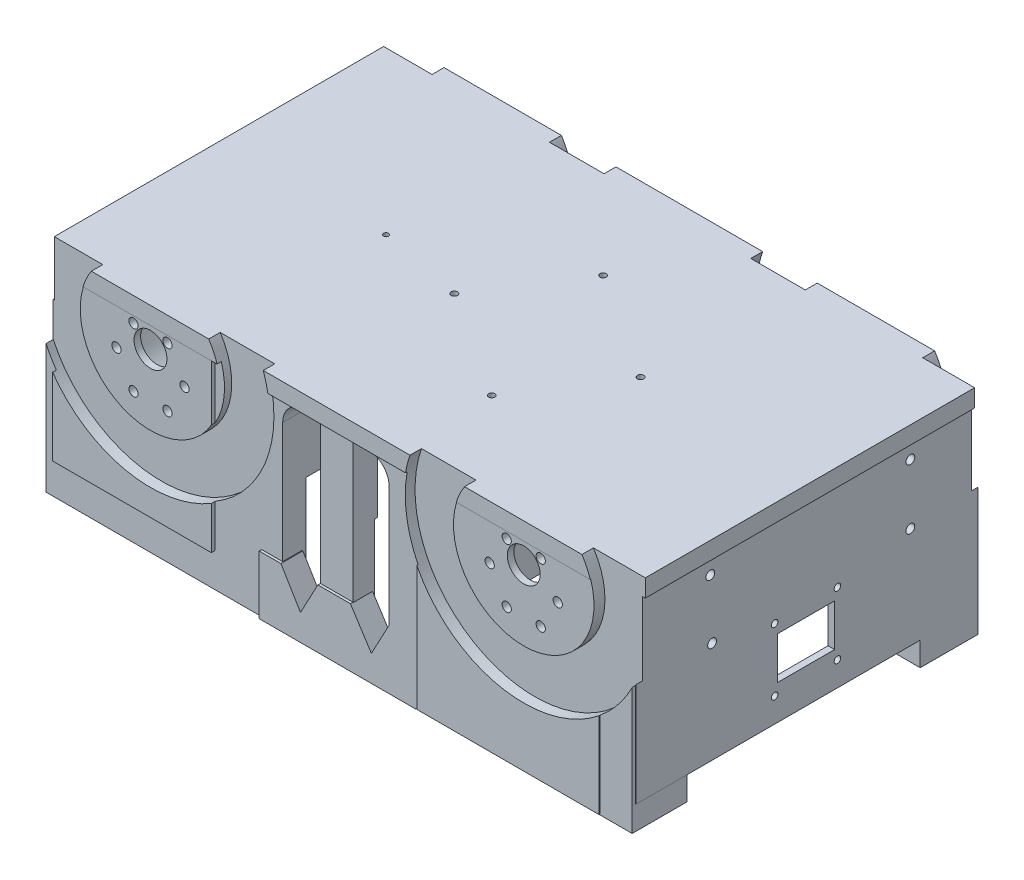
SolidWorks part; units mm, degrees
ref_plane "Front Plane" through (0, 0, 0) normal (0, 0, 1) x (1, 0, 0)
ref_plane "Top Plane" through (0, 0, 0) normal (0, 1, 0) x (1, 0, 0)
ref_plane "Right Plane" through (0, 0, 0) normal (1, 0, 0) x (0, 0, -1)
sketch "MotorHoldersSketch" plane through (0, 0, 0) normal (0, 0, 1) x (1, 0, 0)
  line L0 (0, 0) -> (170, 0) construction
  line L1 (0, 0) -> (0, 23.41) construction
  line L2 (170, 0) -> (170, 23.41) construction
  circle A0 centre (0, 0) radius 23.41
  circle A1 centre (170, 0) radius 23.41
ref_axis "MotorCenterAxis1" through (0, 0, 0) along (0, 0, 1)
ref_axis "MotorCenterAxis2" through (170, 0, 0) along (0, 0, 1)
extrude "MotorHolders" add sketch "MotorHoldersSketch" along normal blind 80 and the other way blind 80
sketch "Sketch3" plane through (0, 0, 0) normal (0, 0, 1) x (1, 0, 0)
  line L1 (1.9406, 21.133) -> (168.3435, 21.133)
  line L2 (1.9406, 21.133) -> (1.9406, 18.3155)
  line L3 (1.9406, 18.3155) -> (168.3435, 18.3155)
  line L4 (168.3435, 21.133) -> (168.3435, 18.3155)
sketch "Sketch4" plane through (0, 0, 0) normal (0, 1, 0) x (1, 0, 0)
  line L1 (221.2811, -76.3794) -> (-41.4939, -76.3794)
  line L2 (221.2811, -76.3794) -> (221.2811, 76.7331)
  line L3 (221.2811, 76.7331) -> (-41.4939, 76.7331)
  line L4 (-41.4939, -76.3794) -> (-41.4939, 76.7331)
extrude "Cut-Extrude1" cut sketch "Sketch4" against normal blind 26
ref_axis "Axis3" through (170, 0, 0) along (0, -1, 0)
sketch3d "ReferencePlanePosition"
  line L0 (170, 0, 0) -> (170, -34.8293, 0)
  line L1 (170, 0, 0) -> (170, -38.994, 0) construction
ref_plane "ReferencePlane" through (170, -34.8293, 0) normal (0, -1, 0) x (-1, 0, 0)
sketch "Sketch6" plane through (170, -34.8293, 0) normal (0, -1, 0) x (-1, 0, 0)
  line L1 (219.5858, 78.949) -> (112.1002, 78.949)
  line L2 (219.5858, 78.949) -> (219.5858, 65.5282)
  line L3 (219.5858, 65.5282) -> (112.1002, 65.5282)
  line L4 (112.1002, 78.949) -> (112.1002, 65.5282)
  line L5 (219.3147, -40.0209) -> (111.499, -40.0209)
  line L6 (219.3147, -40.0209) -> (219.3147, -78.2822)
  line L7 (219.3147, -78.2822) -> (111.499, -78.2822)
  line L8 (111.499, -40.0209) -> (111.499, -78.2822)
  line L9 (61.4891, 77.8627) -> (19.9904, 77.8627)
  line L10 (61.4891, 77.8627) -> (61.4891, 40.7512)
  line L11 (61.4891, 40.7512) -> (19.9904, 40.7512)
  line L12 (19.9904, 77.8627) -> (19.9904, 40.7512)
  line L13 (61.8484, -44.1716) -> (20.0852, -44.1716)
  line L14 (61.8484, -44.1716) -> (61.8484, -79.4437)
  line L15 (61.8484, -79.4437) -> (20.0852, -79.4437)
  line L16 (20.0852, -44.1716) -> (20.0852, -79.4437)
  line L17 (213.765, 73.0364) -> (192.9548, 73.0364)
  line L18 (213.765, 73.0364) -> (213.765, 71.0153)
  line L19 (213.765, 71.0153) -> (192.9548, 71.0153)
  line L20 (192.9548, 73.0364) -> (192.9548, 71.0153)
  line L21 (41.3552, 69.1777) -> (28.5109, 69.1777)
  line L22 (41.3552, 69.1777) -> (41.3552, 50.8413)
  line L23 (41.3552, 50.8413) -> (28.5109, 50.8413)
  line L24 (28.5109, 69.1777) -> (28.5109, 50.8413)
  line L25 (43.3068, -72.8101) -> (32.1723, -72.8101)
  line L26 (43.3068, -72.8101) -> (43.3068, -54.7747)
  line L27 (43.3068, -54.7747) -> (32.1723, -54.7747)
  line L28 (32.1723, -72.8101) -> (32.1723, -54.7747)
  line L29 (211.9411, -70.4881) -> (201.0982, -70.4881)
  line L30 (211.9411, -70.4881) -> (211.9411, -60.1404)
  line L31 (211.9411, -60.1404) -> (201.0982, -60.1404)
  line L32 (201.0982, -70.4881) -> (201.0982, -60.1404)
  line L33 (97.1795, 78.949) -> (79.4162, 78.949)
  line L34 (97.1795, 78.949) -> (97.1795, 67.7632)
  line L35 (97.1795, 67.7632) -> (79.4162, 67.7632)
  line L36 (79.4162, 78.949) -> (79.4162, 67.7632)
  line L37 (58.6711, 51.3198) -> (53.8697, 51.3198)
  line L38 (58.6711, 51.3198) -> (58.6711, 67.7632)
  line L39 (58.6711, 67.7632) -> (53.8697, 67.7632)
  line L40 (53.8697, 51.3198) -> (53.8697, 67.7632)
  line L41 (94.2281, -78.2822) -> (79.4162, -78.2822)
  line L42 (94.2281, -78.2822) -> (94.2281, -67.2515)
  line L43 (94.2281, -67.2515) -> (79.4162, -67.2515)
  line L44 (79.4162, -78.2822) -> (79.4162, -67.2515)
  line L45 (56.3648, -69.8638) -> (51.7107, -69.8638)
  line L46 (56.3648, -69.8638) -> (56.3648, -55.4273)
  line L47 (56.3648, -55.4273) -> (51.7107, -55.4273)
  line L48 (51.7107, -69.8638) -> (51.7107, -55.4273)
  line L49 (-20.7001, -79.4437) -> (-48.8506, -79.4437)
  line L50 (-20.7001, -79.4437) -> (-20.7001, -54.5097)
  line L51 (-20.7001, -54.5097) -> (-48.8506, -54.5097)
  line L52 (-48.8506, -79.4437) -> (-48.8506, -54.5097)
  line L53 (-18.3873, 77.8627) -> (-49.0581, 77.8627)
  line L54 (-18.3873, 77.8627) -> (-18.3873, 51.5325)
  line L55 (-18.3873, 51.5325) -> (-49.0581, 51.5325)
  line L56 (-49.0581, 77.8627) -> (-49.0581, 51.5325)
  line L57 (-41.8141, -72.8101) -> (-31.6362, -72.8101)
  line L58 (-41.8141, -72.8101) -> (-41.8141, -62.9794)
  line L59 (-41.8141, -62.9794) -> (-31.6362, -62.9794)
  line L60 (-31.6362, -72.8101) -> (-31.6362, -62.9794)
  line L61 (-31.6362, 69.1777) -> (-41.5347, 69.1777)
  line L62 (-31.6362, 69.1777) -> (-31.6362, 58.5421)
  line L63 (-31.6362, 58.5421) -> (-41.5347, 58.5421)
  line L64 (-41.5347, 69.1777) -> (-41.5347, 58.5421)
extrude "PowerBankHolders" add sketch "Sketch6" along normal blind 40 and the other way blind 59 separate body
sketch3d "3DSketch3"
  line L0 (170, 0, 0) -> (170, -64.5, 0) construction
ref_plane "Plane2" through (170, -64.5, 0) normal (0, -1, 0) x (-1, 0, 0)
sketch "Sketch7" plane through (170, -64.5, 0) normal (0, -1, 0) x (-1, 0, 0)
  line L1 (-9.5047, -80.801) -> (181.32, -80.801)
  line L2 (-9.5047, -80.801) -> (-9.5047, 73.8662)
  line L3 (-9.5047, 73.8662) -> (181.32, 73.8662)
  line L4 (181.32, -80.801) -> (181.32, 73.8662)
  line L5 (151.8712, -54.3972) -> (26.5361, -54.3972)
  line L6 (151.8712, -54.3972) -> (151.8712, 46.2413)
  line L7 (151.8712, 46.2413) -> (26.5361, 46.2413)
  line L8 (26.5361, -54.3972) -> (26.5361, 46.2413)
ref_point "Point1"
ref_point "Point2"
sketch3d "3DSketch11"
  line L0 (0, 0, -80) -> (170, 0, 80) construction
  point P4 (85, 0, 0)
sketch "MotorHolderExtrudeSketch" plane through (0, 0, 0) normal (0, 0, 1) x (1, 0, 0)
  circle A0 centre (170, 0) radius 20.415
  circle A1 centre (0, 0) radius 20.415
  circle A3 centre (0, 0) radius 23.41 construction
  circle A4 centre (170, 0) radius 23.41 construction
ref_point "TopOfMotors"
ref_plane "TangentToTopOfMotors" through (0, -20.415, 0) normal (0, 1, 0) x (1, 0, 0)
ref_axis "Axis4" through (85, 0, 0) along (0, -1, 0)
ref_plane "BottomOfPowerBankRegion" through (0, -20.425, 0) normal (0, 1, 0) x (1, 0, 0)
ref_point "CenterAtBottomOfPowerBank"
ref_plane "TopOfPowerBankPlane" through (0, -54.425, 0) normal (0, 1, 0) x (1, 0, 0)
sketch "Sketch13" plane through (0, -54.425, 0) normal (0, 1, 0) x (1, 0, 0)
  line L1 (-19.4498, 72.5454) -> (166.1636, 72.5454)
  line L2 (-19.4498, 72.5454) -> (-19.4498, -78.2051)
  line L3 (-19.4498, -78.2051) -> (166.1636, -78.2051)
  line L4 (166.1636, 72.5454) -> (166.1636, -78.2051)
  line L5 (19.3173, -49.583) -> (137.9607, -49.583)
  line L6 (19.3173, -49.583) -> (19.3173, -21.0549)
  line L7 (19.3173, -21.0549) -> (137.9607, -21.0549)
  line L8 (137.9607, -49.583) -> (137.9607, -21.0549)
  line L9 (19.3173, 56.6778) -> (137.9607, 56.6778)
  line L10 (19.3173, 56.6778) -> (19.3173, 36.3234)
  line L11 (19.3173, 36.3234) -> (137.9607, 36.3234)
  line L12 (137.9607, 56.6778) -> (137.9607, 36.3234)
  line L13 (19.3173, 18.3186) -> (137.9607, 18.3186)
  line L14 (19.3173, 18.3186) -> (19.3173, -7.3615)
  line L15 (19.3173, -7.3615) -> (137.9607, -7.3615)
  line L16 (137.9607, 18.3186) -> (137.9607, -7.3615)
sketch "Sketch15" plane through (150.0096, 0, 0) normal (1, 0, 0) x (0, 0, -1)
  line L1 (72.5313, -25.7765) -> (45.7099, -25.7765)
  line L2 (72.5313, -25.7765) -> (72.5313, -24.2242)
  line L3 (72.5313, -24.2242) -> (45.7099, -24.2242)
  line L4 (45.7099, -25.7765) -> (45.7099, -24.2242)
ref_plane "Plane6" through (0, 0, 0) normal (0, 0, 1) x (1, 0, 0)
sketch "MotorGeometry1" plane through (0, 0, 0) normal (0, 0, 1) x (1, 0, 0)
  line L0 (170, 0) -> (170, -13.42)
  line L1 (170, 0) -> (170, -34.8293) construction
  line L2 (170, -13.42) -> (162.25, -13.42) construction
  line L3 (170, -13.42) -> (177.75, -13.42) construction
  line L4 (170, -13.42) -> (170, 7) construction
  line L5 (170, 0) -> (185.5, 0) construction
  line L6 (170, 0) -> (154.5, 0) construction
  line L7 (170, 0) -> (170, 13.42) construction
  line L8 (170, 0) -> (170, 23.41) construction
  line L9 (170, 13.42) -> (177.75, 13.42) construction
  line L10 (170, 13.42) -> (162.25, 13.42)
ref_axis "BoltAxisA" through (185.5, 0, 0) along (0, 0, 1)
ref_axis "BoltAxisB" through (177.75, -13.42, 0) along (0, 0, 1)
ref_axis "BoltAxisC" through (162.25, -13.42, 0) along (0, 0, 1)
ref_axis "BoltAxisD" through (154.5, 0, 0) along (0, 0, 1)
ref_axis "BoltAxisE" through (162.25, 13.42, 0) along (0, 0, 1)
ref_axis "BoltAxisF" through (177.75, 13.42, 0) along (0, 0, 1)
ref_point "Point6"
ref_point "Point7"
ref_point "Point8"
ref_point "Point9"
ref_point "Point10"
ref_point "Point11"
ref_point "Point12"
ref_point "Point13"
ref_point "Point14"
ref_point "Point15"
ref_point "Point16"
ref_point "Point17"
ref_plane "Plane7" through (0, 0, 0) normal (0, 0, 1) x (1, 0, 0)
sketch "MotorGeometry2" plane through (0, 0, 0) normal (0, 0, 1) x (1, 0, 0)
  line L0 (0, 0) -> (0, -13.42) construction
  line L1 (0, -13.42) -> (7.75, -13.42) construction
  line L2 (0, -13.42) -> (-7.75, -13.42) construction
  line L3 (0, 0) -> (0, 13.42)
  line L4 (0, -13.42) -> (0, 7) construction
  line L5 (0, 13.42) -> (7.75, 13.42) construction
  line L6 (0, 13.42) -> (-7.75, 13.42) construction
  line L7 (0, 0) -> (15.5, 0) construction
  line L8 (0, 0) -> (-15.5, 0) construction
  line L9 (0, 0) -> (0, 23.41) construction
ref_axis "Axis11" through (15.5, 0, 0) along (0, 0, 1)
ref_axis "Axis12" through (7.75, 13.42, 0) along (0, 0, 1)
ref_axis "Axis13" through (-7.75, 13.42, 0) along (0, 0, 1)
ref_axis "Axis14" through (-15.5, 0, 0) along (0, 0, 1)
ref_axis "Axis15" through (-7.75, -13.42, 0) along (0, 0, 1)
ref_axis "Axis16" through (7.75, -13.42, 0) along (0, 0, 1)
ref_point "Point18"
ref_point "Point19"
ref_point "Point20"
ref_point "Point21"
ref_point "Point22"
ref_point "Point23"
ref_point "Point24"
ref_point "Point25"
ref_point "Point26"
ref_point "Point27"
ref_point "Point28"
ref_point "Point29"
ref_plane "BottomPlane" through (0, 19.575, 0) normal (0, 1, 0) x (1, 0, 0)
ref_axis "OutputShaftReference1" through (0, 7, 0) along (0, 0, 1)
ref_point "Point35"
ref_axis "OutputShaftReference2" through (170, 7, 0) along (0, 0, 1)
sketch "Sketch21" plane through (0, 19.575, 0) normal (0, 1, 0) x (1, 0, 0)
  line L0 (219.6842, -79.5488) -> (-50.341, -79.5488) construction
  line L1 (-50.341, -79.5488) -> (-50.341, 79.7899) construction
  line L2 (-50.341, 79.7899) -> (219.6842, 79.7899) construction
  line L3 (219.6842, 79.7899) -> (219.6842, -79.5488) construction
  circle A0 centre (85, 0) radius 156.3953
extrude "BottomPlate" add sketch "Sketch21" along normal blind 5 and the other way blind 3
ref_plane "HoleReferencePlane1" through (0, 0, 80) normal (0, 0, 1) x (1, 0, 0)
ref_point "OutputShaftPosition3"
ref_point "OutputShaftPosition1"
sketch "Sketch23" plane through (0, 0, 80) normal (0, 0, 1) x (1, 0, 0)
  line L1 (27.7411, -59.3229) -> (-44.5901, -59.3229)
  line L2 (27.7411, -59.3229) -> (27.7411, 21.8402)
  line L3 (27.7411, 21.8402) -> (-44.5901, 21.8402)
  line L4 (-44.5901, -59.3229) -> (-44.5901, 21.8402)
  line L5 (121.3218, 21.8402) -> (204.258, 21.8402)
  line L6 (121.3218, 21.8402) -> (121.3218, -74.371)
  line L7 (121.3218, -74.371) -> (204.258, -74.371)
  line L8 (204.258, 21.8402) -> (204.258, -74.371)
extrude "MotorMountingSupport1" add sketch "Sketch23" against normal blind 6
ref_plane "HoleReferencePlane2" through (0, 0, -80) normal (0, 0, -1) x (-1, 0, 0)
ref_point "OutputShaftPosition4"
ref_point "OutputShaftPosition2"
sketch "Sketch24" plane through (0, 0, -80) normal (0, 0, -1) x (-1, 0, 0)
  line L1 (-202.1905, -75.2023) -> (-123.8485, -75.2023)
  line L2 (-202.1905, -75.2023) -> (-202.1905, 19.2374)
  line L3 (-202.1905, 19.2374) -> (-123.8485, 19.2374)
  line L4 (-123.8485, -75.2023) -> (-123.8485, 19.2374)
  line L5 (-24.3642, -64.1521) -> (29.5505, -64.1521)
  line L6 (-24.3642, -64.1521) -> (-24.3642, 22.5226)
  line L7 (-24.3642, 22.5226) -> (29.5505, 22.5226)
  line L8 (29.5505, -64.1521) -> (29.5505, 22.5226)
extrude "MotorMountingSuppor2" add sketch "Sketch24" against normal blind 6
sketch "Sketch17" plane through (0, 0, 80) normal (0, 0, 1) x (1, 0, 0)
  circle A0 centre (185.5, 0) radius 2.1
  circle A1 centre (177.75, -13.42) radius 2.1
  circle A2 centre (162.25, -13.42) radius 2.1
  circle A3 centre (154.5, 0) radius 2.1
  circle A4 centre (162.25, 13.42) radius 2.1
  circle A5 centre (177.75, 13.42) radius 2.1
  circle A6 centre (170, 7) radius 7.5
extrude "MotorHoles1" cut sketch "Sketch17" against normal blind 31.5
sketch "Sketch19" plane through (0, 0, -80) normal (0, 0, -1) x (-1, 0, 0)
  circle A0 centre (-185.5, 0) radius 2.1
  circle A1 centre (-177.75, -13.42) radius 2.1
  circle A2 centre (-162.25, -13.42) radius 2.1
  circle A3 centre (-154.5, 0) radius 2.1
  circle A4 centre (-162.25, 13.42) radius 2.1
  circle A5 centre (-177.75, 13.42) radius 2.1
  circle A6 centre (-170, 7) radius 7.5
sketch "BoltHolesSketch3" plane through (0, 0, 80) normal (0, 0, 1) x (1, 0, 0)
  circle A0 centre (7.75, -13.42) radius 2.1
  circle A1 centre (15.5, 0) radius 2.1
  circle A2 centre (7.75, 13.42) radius 2.1
  circle A3 centre (-7.75, 13.42) radius 2.1
  circle A4 centre (-15.5, 0) radius 2.1
  circle A5 centre (-7.75, -13.42) radius 2.1
  circle A6 centre (0, 7) radius 7.5
extrude "Cut-Extrude4" cut sketch "Sketch19" against normal blind 30
extrude "MotorHoles3" cut sketch "BoltHolesSketch3" against normal blind 31.5
sketch "BoltHolesSketch4" plane through (0, 0, -80) normal (0, 0, -1) x (-1, 0, 0)
  circle A0 centre (-15.5, 0) radius 2.1
  circle A1 centre (-7.75, 13.42) radius 2.1
  circle A2 centre (7.75, 13.42) radius 2.1
  circle A3 centre (15.5, 0) radius 2.1
  circle A4 centre (7.75, -13.42) radius 2.1
  circle A5 centre (-7.75, -13.42) radius 2.1
  circle A6 centre (0, 7) radius 7.5
extrude "MotorHoles4" cut sketch "BoltHolesSketch4" against normal blind 15
ref_plane "Front" through (219.0581, 0, 0) normal (1, 0, 0) x (0, 0, -1)
sketch "Sketch29" plane through (219.0581, 0, 0) normal (1, 0, 0) x (0, 0, -1)
  line L1 (76.6955, -63.9254) -> (-77.9397, -63.9254)
  line L2 (76.6955, -63.9254) -> (76.6955, 20.2062)
  line L3 (76.6955, 20.2062) -> (-77.9397, 20.2062)
  line L4 (-77.9397, -63.9254) -> (-77.9397, 20.2062)
  line L5 (-13.4507, -48.1531) -> (12.5493, -48.1531)
  line L6 (-13.4507, -48.1531) -> (-13.4507, -28.9404)
  line L7 (-13.4507, -28.9404) -> (12.5493, -28.9404)
  line L8 (12.5493, -48.1531) -> (12.5493, -28.9404)
extrude "Boss-Extrude8" add sketch "Sketch29" against normal blind 3
ref_plane "RaspberryPiBasePlane" through (0, 16.575, 0) normal (0, -1, 0) x (-1, 0, 0)
sketch "Sketch27" plane through (0, 16.575, 0) normal (0, -1, 0) x (-1, 0, 0)
  line L1 (31.6337, 64.5517) -> (-194.8264, 64.5517)
  line L2 (31.6337, 64.5517) -> (31.6337, -65.4335)
  line L3 (31.6337, -65.4335) -> (-194.8264, -65.4335)
  line L4 (-194.8264, 64.5517) -> (-194.8264, -65.4335)
extrude "Boss-Extrude6" add sketch "Sketch27" against normal blind 3
ref_plane "Plane12" through (0, -74.8293, 0) normal (0, -1, 0) x (-1, 0, 0)
sketch "Sketch28" plane through (0, -74.8293, 0) normal (0, -1, 0) x (-1, 0, 0)
  line L1 (-189.3897, -97.3973) -> (-123.0026, -97.3973)
  line L2 (-189.3897, -97.3973) -> (-189.3897, 96.7192)
  line L3 (-189.3897, 96.7192) -> (-123.0026, 96.7192)
  line L4 (-123.0026, -97.3973) -> (-123.0026, 96.7192)
sketch "Sketch40" plane through (0, 16.575, 0) normal (0, -1, 0) x (1, 0, 0)
  line L1 (-49.5858, -65.5282) -> (-15.7443, -65.5282)
  line L2 (-49.5858, -65.5282) -> (-49.5858, -33.9964)
  line L3 (-49.5858, -33.9964) -> (-15.7443, -33.9964)
  line L4 (-15.7443, -65.5282) -> (-15.7443, -33.9964)
extrude "Boss-Extrude11" add sketch "Sketch40" along normal blind 40
fillet "Fillet2" radius 15 1 edges at (-33.0588, 16.575, -33.9964) type face fillet first side face at (-28.7089, -2.1691, -33.9964) second side face at (85, 16.575, 156.3953)
fillet "Fillet3" radius 15 1 edges at (-32.6651, -23.425, -65.5282) type face fillet first side face at (-5.65, -13.42, -65.5282) second side face at (-32.6651, -23.425, -49.7623)
sketch "Sketch11" plane through (0, -20.425, 0) normal (0, 1, 0) x (1, 0, 0)
  line L0 (-34.2162, 4.2922) -> (204.2162, -4.2922) construction
  line L5 (-34.2162, -64.7581) -> (-34.2162, 73.3425)
  line L6 (204.2162, 63.611) -> (204.2162, -72.1954)
  line L7 (204.2162, -72.1954) -> (-34.2162, -64.7581)
  line L8 (204.2162, 63.611) -> (-34.2162, 73.3425)
  circle A0 centre (85, 0) radius 104 construction
extrude "PowerBankCut" cut sketch "Sketch11" against normal up to surface (54.4043 mm away) up to face at (204.7754, -74.8293, 66.9767)
extrude "MotorHolderCut" cut sketch "MotorHolderExtrudeSketch" against normal blind 77 and the other way blind 77
sketch "Sketch31" plane through (219.0581, 0, 0) normal (1, 0, 0) x (0, 0, -1)
  line L0 (-11.9853, 13.4398) -> (-13.3624, 12.0627)
  line L1 (-13.3624, 12.0627) -> (-13.3624, 8.9452)
  line L2 (-11.9853, 6.9748) -> (-13.3624, 8.9452)
  line L3 (23.5583, 6.7877) -> (23.5583, 13.4398)
  line L4 (23.5583, 13.4398) -> (19.9736, 13.4398)
  line L5 (19.9736, 13.4398) -> (19.9736, 12.0236)
  line L6 (19.9736, 12.0236) -> (22.4953, 12.0236)
  line L7 (22.4953, 12.0236) -> (22.4953, 6.7877)
  line L8 (23.5583, 6.7877) -> (22.4953, 6.7877)
  line L9 (19.3464, 13.4398) -> (19.3464, 6.7877)
  line L10 (19.3464, 6.7877) -> (16.5174, 6.7877)
  line L11 (16.5174, 6.7877) -> (16.5174, 7.9482)
  line L12 (16.5174, 7.9482) -> (18.3741, 7.9482)
  line L13 (18.3741, 7.9482) -> (18.3741, 9.5315)
  line L14 (18.3741, 9.5315) -> (16.5174, 9.5315)
  line L15 (16.5174, 9.5315) -> (16.5174, 10.6274)
  line L16 (16.5174, 10.6274) -> (18.3741, 10.6274)
  line L17 (18.3741, 10.6274) -> (18.3741, 12.0236)
  line L18 (18.3741, 12.0236) -> (16.5174, 12.0236)
  line L19 (16.5174, 12.0236) -> (16.5174, 13.4398)
  line L20 (19.3464, 13.4398) -> (16.5174, 13.4398)
  line L21 (15.6231, 6.7877) -> (15.6231, 7.9482)
  line L22 (15.6231, 6.7877) -> (12.7162, 6.7877)
  line L23 (12.7162, 6.7877) -> (12.7162, 7.9482)
  line L24 (12.7162, 7.9482) -> (13.819, 7.9482)
  line L25 (13.819, 7.9482) -> (13.819, 13.4398)
  line L26 (13.819, 13.4398) -> (14.771, 13.4398)
  line L27 (14.771, 13.4398) -> (14.771, 7.9482)
  line L28 (15.6231, 7.9482) -> (14.771, 7.9482)
  line L29 (9.0737, 7.9482) -> (10.2342, 6.7877)
  line L30 (10.2342, 6.7877) -> (11.2446, 6.7877)
  line L31 (11.2446, 6.7877) -> (12.156, 7.699)
  line L32 (12.156, 7.699) -> (12.156, 9.5315)
  line L33 (12.156, 9.5315) -> (10.2342, 10.8736)
  line L34 (9.0737, 7.9482) -> (10.2342, 7.9482)
  line L35 (10.2342, 7.9482) -> (10.6704, 7.699)
  line L36 (10.6704, 7.699) -> (11.2446, 8.0737)
  line L37 (11.2446, 8.0737) -> (9.0737, 11.4008)
  line L38 (9.0737, 11.4008) -> (9.6875, 13.4398)
  line L39 (9.6875, 13.4398) -> (11.4814, 13.4398)
  line L40 (11.4814, 13.4398) -> (12.156, 12.3409)
  line L41 (12.156, 12.3409) -> (11.2446, 12.3409)
  line L42 (11.2446, 12.3409) -> (10.6704, 12.772)
  line L43 (10.6704, 12.772) -> (10.1086, 12.0236)
  line L44 (10.1086, 12.0236) -> (10.2342, 10.8736)
  line L45 (-20.664, 6.9748) -> (-20.664, 8.0737)
  line L46 (-18.6605, 13.4398) -> (-19.6346, 13.4398)
  line L47 (-18.6605, 13.4398) -> (-18.6605, 12.3409)
  line L48 (-18.6605, 12.3409) -> (-19.6346, 12.3409)
  line L49 (-19.6346, 13.4398) -> (-19.6346, 12.3409)
  line L50 (-20.664, 8.0737) -> (-22.0801, 8.0737)
  line L51 (-20.664, 6.9748) -> (-24.6188, 6.9748)
  line L52 (-24.6188, 6.9748) -> (-24.6188, 8.0737)
  line L53 (-24.6188, 8.0737) -> (-23.2262, 8.0737)
  line L54 (-22.0801, 8.0737) -> (-22.0801, 13.4398)
  line L55 (-22.0801, 13.4398) -> (-23.2262, 13.4398)
  line L56 (8.0122, 13.4398) -> (8.253, 6.7877)
  line L57 (8.253, 6.7877) -> (6.0128, 6.7877)
  line L58 (6.0128, 6.7877) -> (4.2685, 7.9482)
  line L59 (4.2685, 7.9482) -> (3.8991, 9.7863)
  line L60 (3.8991, 9.7863) -> (5.5426, 10.6274)
  line L61 (5.5426, 10.6274) -> (3.8991, 13.4398)
  line L62 (3.8991, 13.4398) -> (5.5426, 13.4398)
  line L63 (5.5426, 13.4398) -> (6.5701, 10.6274)
  line L64 (6.5701, 10.6274) -> (7.1329, 10.6274)
  line L65 (7.1329, 10.6274) -> (7.0311, 13.4398)
  line L66 (7.0311, 13.4398) -> (8.0122, 13.4398)
  line L67 (1.6684, 13.4398) -> (-0.1827, 13.4398)
  line L68 (-0.1827, 13.4398) -> (-1.6538, 10.8736)
  line L69 (-1.6538, 10.8736) -> (-1.6538, 8.4246)
  line L70 (-1.6538, 8.4246) -> (-0.1827, 6.9535)
  line L71 (-0.1827, 6.9535) -> (1.6684, 6.9535)
  line L72 (1.6684, 6.9535) -> (2.9495, 8.2346)
  line L73 (2.9495, 8.2346) -> (2.9495, 10.6274)
  line L74 (2.9495, 10.6274) -> (1.6684, 13.4398)
  line L75 (-2.9468, 6.9535) -> (-2.9468, 13.4398)
  line L76 (-2.9468, 13.4398) -> (-5.696, 13.4398)
  line L77 (-5.696, 13.4398) -> (-7.1123, 12.0236)
  line L78 (-7.1123, 12.0236) -> (-7.1123, 10.6274)
  line L79 (-7.1123, 10.6274) -> (-5.9341, 9.4492)
  line L80 (-5.9341, 9.4492) -> (-7.1123, 8.2711)
  line L81 (-7.1123, 8.2711) -> (-7.1123, 7.9482)
  line L82 (-7.1123, 7.9482) -> (-5.696, 6.9535)
  line L83 (-5.696, 6.9535) -> (-2.9468, 6.9535)
  line L84 (-9.9534, 6.9535) -> (-8.8331, 8.0737)
  line L85 (-8.8331, 8.0737) -> (-8.8331, 12.3409)
  line L86 (-8.8331, 12.3409) -> (-10.7011, 13.4398)
  line L87 (-10.7011, 13.4398) -> (-11.9853, 13.4398)
  line L88 (-23.2262, 13.4398) -> (-23.2262, 8.0737)
  line L89 (-25.5187, 6.9748) -> (-26.5366, 13.4398)
  line L90 (-26.5366, 13.4398) -> (-27.8126, 13.4398)
  line L91 (-11.9853, 6.9748) -> (-9.9534, 6.9535)
  line L92 (-14.5404, 6.9748) -> (-18.6605, 6.9748)
  line L93 (-18.6605, 6.9748) -> (-18.6605, 8.0737)
  line L94 (-18.6605, 8.0737) -> (-17.3325, 8.0737)
  line L95 (-17.3325, 8.0737) -> (-17.3325, 13.4398)
  line L96 (-17.3325, 13.4398) -> (-16.1754, 13.4398)
  line L97 (-16.1754, 13.4398) -> (-16.1754, 8.0737)
  line L98 (-16.1754, 8.0737) -> (-14.5404, 8.0737)
  line L99 (-14.5404, 8.0737) -> (-14.5404, 6.9748)
  line L100 (1.1066, 8.2346) -> (1.8172, 8.9452)
  line L101 (1.8172, 8.9452) -> (1.8172, 11.1371)
  line L102 (1.8172, 11.1371) -> (0.8255, 12.1288)
  line L103 (0.8255, 12.1288) -> (0.2118, 12.1288)
  line L104 (0.2118, 12.1288) -> (-0.525, 11.1371)
  line L105 (-0.525, 11.1371) -> (-0.6294, 9.2253)
  line L106 (-0.6294, 9.2253) -> (0.0159, 8.2739)
  line L107 (0.0159, 8.2739) -> (1.1066, 8.2346)
  line L108 (-4.0608, 9.2253) -> (-5.4172, 9.2253)
  line L109 (-5.4172, 9.2253) -> (-5.696, 8.4246)
  line L110 (-5.696, 8.4246) -> (-4.9992, 7.9482)
  line L111 (-4.9992, 7.9482) -> (-4.0608, 7.9482)
  line L112 (-4.0608, 7.9482) -> (-4.0608, 9.2253)
  line L113 (-3.8961, 10.3794) -> (-3.8961, 12.1288)
  line L114 (-3.8961, 12.1288) -> (-5.5739, 12.3409)
  line L115 (-5.5739, 12.3409) -> (-6.0661, 11.2541)
  line L116 (-6.0661, 11.2541) -> (-5.257, 10.3794)
  line L117 (-5.257, 10.3794) -> (-3.8961, 10.3794)
  line L118 (-10.3458, 8.2739) -> (-9.9534, 8.9452)
  line L119 (-9.9534, 8.9452) -> (-9.9534, 11.8216)
  line L120 (-9.9534, 11.8216) -> (-10.9018, 12.3409)
  line L121 (-10.9018, 12.3409) -> (-11.4919, 12.3409)
  line L122 (-11.4919, 12.3409) -> (-12.1481, 11.6848)
  line L123 (-12.1481, 11.6848) -> (-11.9853, 8.9452)
  line L124 (-11.9853, 8.9452) -> (-11.4919, 8.2739)
  line L125 (-11.4919, 8.2739) -> (-10.3458, 8.2739)
  line L126 (7.1329, 7.9482) -> (7.1329, 9.5315)
  line L127 (7.1329, 9.5315) -> (6.0128, 9.5315)
  line L128 (6.0128, 9.5315) -> (5.5426, 9.0613)
  line L129 (5.5426, 9.0613) -> (5.5426, 8.4246)
  line L130 (5.5426, 8.4246) -> (6.0932, 7.874)
  line L131 (6.0932, 7.874) -> (7.1329, 7.9482)
  line L132 (-27.8126, 13.4398) -> (-29.1855, 6.9748)
  line L133 (-29.1855, 6.9748) -> (-27.8126, 6.9748)
  line L134 (-27.8126, 6.9748) -> (-27.1746, 11.2541)
  line L135 (-27.1746, 11.2541) -> (-26.5008, 6.9748)
  line L136 (-26.5008, 6.9748) -> (-25.5187, 6.9748)
sketch "Sketch32" plane through (0, 19.575, 0) normal (0, 1, 0) x (1, 0, 0)
  line L1 (-48.8137, 80.4301) -> (220.392, 80.4301)
  line L2 (-48.8137, 80.4301) -> (-48.8137, -80.215)
  line L3 (-48.8137, -80.215) -> (220.392, -80.215)
  line L4 (220.392, 80.4301) -> (220.392, -80.215)
  line L5 (283.5566, -218.7268) -> (-136.4889, -218.7268)
  line L8 (-136.4889, -218.7268) -> (-136.4889, 206.3198)
  line L10 (283.5566, 206.3198) -> (283.5566, -218.7268)
  line L13 (283.5566, 206.3198) -> (-136.4889, 206.3198)
extrude "BaseDefiningCut" cut sketch "Sketch32" along normal blind 20 and the other way blind 20
sketch "Sketch39" plane through (0, 16.575, 0) normal (0, -1, 0) x (1, 0, 0)
  line L1 (-48.8137, -65.5282) -> (-16.0867, -65.5282)
  line L2 (-48.8137, -65.5282) -> (-48.8137, -46.28)
  line L3 (-48.8137, -46.28) -> (-16.0867, -46.28)
  line L4 (-16.0867, -65.5282) -> (-16.0867, -46.28)
sketch "Sketch35" plane through (0, 0, -80.4301) normal (0, 0, -1) x (-1, 0, 0)
  line L0 (69.0502, 16.3777) -> (-36.4474, 27.6206)
  line L1 (-36.4474, 27.6206) -> (71.6404, 26.1593)
  line L2 (69.0502, 16.3777) -> (71.6404, 26.1593)
  line L3 (-223.8844, 30.8145) -> (-223.8844, 17.5678)
  line L4 (-223.8844, 17.5678) -> (-116.0163, 30.8145)
  line L5 (-116.0163, 30.8145) -> (-223.8844, 30.8145)
sketch "Sketch36" plane through (-49.3147, 0, 0) normal (-1, 0, 0) x (0, 0, 1)
  line L0 (40.0209, -74.8293) -> (40.0209, -38.3689) construction
  line L1 (55.0666, -55.0742) -> (78.2822, -55.0742) construction
  line L2 (40.0209, -38.3689) -> (40.0209, -74.8293) construction
  line L3 (78.2822, -0.425) -> (78.2822, -74.8293) construction
  line L4 (55.0666, -55.0742) -> (55.0666, -16.2943) construction
  circle A1 centre (55.0666, -55.0742) radius 14
extrude "HoleForPowerConnector" cut sketch "Sketch36" against normal blind 17
sketch "Sketch37" plane through (0, -20.425, 0) normal (0, -1, 0) x (1, 0, 0)
  line L1 (144.416, -35.6729) -> (89.0759, -35.6729)
  line L2 (144.416, -35.6729) -> (144.416, -65.4438)
  line L3 (144.416, -65.4438) -> (89.0759, -65.4438)
  line L4 (89.0759, -35.6729) -> (89.0759, -65.4438)
extrude "Cut-Extrude7" cut sketch "Sketch37" against normal blind 36
sketch "Sketch38" plane through (0, 16.575, 0) normal (0, -1, 0) x (1, 0, 0)
  line L0 (25.9964, 80.215) -> (25.9964, -1.3165) construction
  line L1 (-48.8137, 80.215) -> (219.2574, 80.215) construction
  circle A0 centre (25.9964, -1.3165) radius 1.1452
extrude "Cut-Extrude8" cut sketch "Sketch38" against normal blind 10
sketch "Sketch41" plane through (0, 0, 80) normal (0, 0, 1) x (1, 0, 0)
  circle A0 centre (0, 7) radius 32
  circle A1 centre (0, 7) radius 54.5
extrude "SpaceForWheel1" cut sketch "Sketch41" against normal blind 5 and the other way blind 10
sketch "Sketch42" plane through (0, 0, 80) normal (0, 0, 1) x (1, 0, 0)
  circle A0 centre (170, 7) radius 32
  circle A1 centre (170, 7) radius 54.5
extrude "Cut-Extrude10" cut sketch "Sketch42" against normal blind 5 and the other way blind 10
sketch "Sketch43" plane through (0, 0, -80) normal (0, 0, -1) x (-1, 0, 0)
  circle A0 centre (-170, 7) radius 32
  circle A1 centre (-170, 7) radius 54.5
extrude "Cut-Extrude11" cut sketch "Sketch43" against normal blind 5 and the other way blind 10
sketch "Sketch44" plane through (0, 0, -80) normal (0, 0, -1) x (-1, 0, 0)
  circle A0 centre (0, 7) radius 32
  circle A1 centre (0, 7) radius 54.5
extrude "Cut-Extrude12" cut sketch "Sketch44" against normal blind 5 and the other way blind 10
sketch "Sketch45" plane through (-48.8137, 0, 0) normal (-1, 0, 0) x (0, 0, 1)
  line L0 (-75, 24.575) -> (75, 24.575) construction
  line L1 (-72.1063, 24.575) -> (42.0312, 24.575)
  line L2 (-72.1063, 24.575) -> (-72.1063, -74.1222)
  line L3 (-72.1063, -74.1222) -> (42.0312, -74.1222)
  line L4 (42.0312, 24.575) -> (42.0312, -74.1222)
extrude "BackPlate" add sketch "Sketch45" against normal blind 2
sketch "Sketch46" plane through (0, -74.8293, 0) normal (0, -1, 0) x (1, 0, 0)
  line L1 (97.1427, -74.9256) -> (213.5256, -74.9256)
  line L2 (97.1427, -74.9256) -> (97.1427, -71.5234)
  line L3 (97.1427, -71.5234) -> (213.5256, -71.5234)
  line L4 (213.5256, -74.9256) -> (213.5256, -71.5234)
  line L5 (97.1427, 72.8226) -> (213.5256, 72.8226)
  line L6 (97.1427, 72.8226) -> (97.1427, 77.4687)
  line L7 (97.1427, 77.4687) -> (213.5256, 77.4687)
  line L8 (213.5256, 72.8226) -> (213.5256, 77.4687)
fillet "Fillet8" radius 10 1 edges at (57.8998, 16.575, -72.2386) type face fillet first side face at (57.8998, -26.2264, -71.3533) second side face at (25.9964, 16.575, -2.4617)
fillet "Fillet9" radius 10 1 edges at (108.5109, 16.575, -59.3069) type face fillet first side face at (108.5109, -15.7761, -62.8937) second side face at (25.9964, 16.575, -2.4617)
fillet "Fillet10" radius 10 1 edges at (108.1516, 16.575, 61.8076) type face fillet first side face at (108.1516, -26.2264, 64.2714) second side face at (25.9964, 16.575, -2.4617)
sketch "Sketch49" plane through (0, 0, 80) normal (0, 0, 1) x (1, 0, 0)
  line L0 (27.7411, -8.9509) -> (27.7411, 16.575) construction
  circle A0 centre (27.7411, 12.953) radius 3.5831
fillet "Fillet11" radius 10 1 edges at (58.501, 16.575, 59.1515) type face fillet first side face at (58.501, -26.2264, 61.9844) second side face at (25.9964, 16.575, -2.4617)
sketch "Sketch50" plane through (0, -74.8293, 0) normal (0, -1, 0) x (1, 0, 0)
  line L1 (-49.3147, 40.0209) -> (-40.7689, 40.0209)
  line L2 (-49.3147, 40.0209) -> (-49.3147, 52.7795)
  line L3 (-49.3147, 52.7795) -> (-40.7689, 52.7795)
  line L4 (-40.7689, 40.0209) -> (-40.7689, 52.7795)
  line L5 (-49.5858, -65.5282) -> (-35.8777, -65.5282)
  line L6 (-49.5858, -65.5282) -> (-49.5858, -77.7316)
  line L7 (-49.5858, -77.7316) -> (-35.8777, -77.7316)
  line L8 (-35.8777, -65.5282) -> (-35.8777, -77.7316)
sketch "Sketch51" plane through (0, 0, 79.4437) normal (0, 0, 1) x (1, 0, 0)
  line L0 (108.1516, -47.9804) -> (100.047, -63.1792)
  line L1 (108.1516, 6.575) -> (108.1516, -74.8293) construction
  line L2 (100.047, -63.1792) -> (90.5163, -48.3368)
  line L3 (90.5163, -48.3368) -> (75.6762, -48.3368)
  line L4 (75.6762, -48.3368) -> (67.7615, -63.1792)
  line L5 (67.7615, -63.1792) -> (58.8398, -48.3368)
  line L6 (58.8398, -48.3368) -> (48.9291, -48.3368)
  line L7 (48.9291, -48.3368) -> (48.9291, -75.0407)
  line L8 (48.9291, -75.0407) -> (120.2514, -75.0407)
  line L9 (120.2514, -75.0407) -> (120.2514, -47.9804)
  line L10 (120.2514, -47.9804) -> (108.1516, -47.9804)
extrude "Boss-Extrude12" add sketch "Sketch51" against normal blind 10
sketch "Sketch53" plane through (0, 0, -77.8627) normal (0, 0, -1) x (-1, 0, 0)
  line L1 (-57.7992, -55.7616) -> (-64.6668, -65.1072)
  line L2 (-64.6668, -65.1072) -> (-72.7541, -55.7616)
  line L3 (-72.7541, -55.7616) -> (-90.6554, -55.7616)
  line L4 (-90.6554, -55.7616) -> (-98.6681, -65.1072)
  line L5 (-98.6681, -65.1072) -> (-108.5109, -55.7616)
  line L6 (-108.5109, 6.575) -> (-108.5109, -74.8293) construction
  line L7 (-108.5109, -55.7616) -> (-123.8485, -55.7616)
  line L8 (-123.8485, -21.9878) -> (-123.8485, -74.8293) construction
  line L9 (-123.8485, -55.7616) -> (-123.8485, -74.8293)
  line L10 (-123.8485, -74.8293) -> (-52.4383, -74.8293)
  line L11 (-52.4383, -74.8293) -> (-52.4383, -55.7616)
  line L12 (-52.4383, -55.7616) -> (-57.7992, -55.7616)
extrude "Boss-Extrude13" add sketch "Sketch53" against normal blind 9
sketch "HolesForRasPiMounting" plane through (0, 16.575, 0) normal (0, -1, 0) x (1, 0, 0)
  circle A0 centre (91.4678, -34.696) radius 1.4146
  circle A1 centre (64.7805, 6.3989) radius 1.4536
  circle A2 centre (140.1107, -3.1069) radius 1.4303
  circle A3 centre (113.4234, 37.9879) radius 1.4064
extrude "Cut-Extrude13" cut sketch "HolesForRasPiMounting" against normal through all
sketch "HolesForChargingPlatesSketch" plane through (219.0581, 0, 0) normal (1, 0, 0) x (0, 0, -1)
  circle A0 centre (47.06, -17.739) radius 2
  circle A1 centre (-43.2542, -17.739) radius 2
  circle A2 centre (-44.0465, 9.5376) radius 2
  circle A3 centre (47.06, 9.5376) radius 2
extrude "HolesForChargingPlates" cut sketch "HolesForChargingPlatesSketch" against normal up to surface (3 mm away) up to face at (216.0581, -23.6752, 1.4886)
sketch "Sketch55" plane through (219.0581, 0, 0) normal (1, 0, 0) x (0, 0, -1)
  line L0 (-13.4507, -48.1531) -> (12.5493, -28.9404) construction
  line L1 (12.5493, -48.1531) -> (-13.4507, -28.9404) construction
ref_point "CamerCutCenter"
ref_axis "CameraCutAxis" through (219.0581, -38.5467, 0.4507) along (1, 0, 0)
sketch "Sketch56" plane through (219.0581, 0, 0) normal (1, 0, 0) x (0, 0, -1)
  line L0 (14.5493, -53.5467) -> (-15.4507, -23.5467) construction
  line L1 (-0.4507, -38.5467) -> (-15.4507, -38.5467) construction
  line L2 (-0.4507, -38.5467) -> (-0.4507, -53.5467) construction
  line L3 (-0.4507, -53.5467) -> (-15.4507, -53.5467) construction
  line L4 (-15.4507, -38.5467) -> (-15.4507, -53.5467) construction
  line L5 (-0.4507, -38.5467) -> (14.5493, -38.5467) construction
  line L6 (-0.4507, -38.5467) -> (-0.4507, -23.5467) construction
  line L7 (-0.4507, -23.5467) -> (14.5493, -23.5467) construction
  line L8 (14.5493, -38.5467) -> (14.5493, -23.5467) construction
  line L9 (-15.4507, -53.5467) -> (14.5493, -53.5467) construction
  line L10 (-15.4507, -53.5467) -> (-15.4507, -23.5467) construction
  line L11 (-15.4507, -23.5467) -> (14.5493, -23.5467) construction
  line L12 (14.5493, -53.5467) -> (14.5493, -23.5467) construction
  line L13 (14.5493, -23.5467) -> (-15.4507, -53.5467) construction
  circle A0 centre (-0.4507, -38.5467) radius 15 construction
  circle A1 centre (-15.4507, -53.5467) radius 1.6 construction
  circle A2 centre (14.5493, -53.5467) radius 1.6 construction
  circle A3 centre (14.5493, -23.5467) radius 1.6 construction
  circle A4 centre (-15.4507, -23.5467) radius 1.6 construction
  circle A5 centre (14.5493, -53.5467) radius 1 construction
  circle A6 centre (-15.4507, -53.5467) radius 1 construction
  circle A7 centre (14.5493, -23.5467) radius 1 construction
  circle A8 centre (-15.4507, -23.5467) radius 1 construction
  circle A9 centre (13.8422, -52.8396) radius 1.5
  circle A10 centre (-14.7436, -52.8396) radius 1.5
  circle A11 centre (-14.7436, -24.2538) radius 1.5
  circle A12 centre (13.8422, -24.2538) radius 1.5
extrude "CameraScrewHoles" cut sketch "Sketch56" against normal up to surface (3 mm away) up to face at (216.0581, -17.739, 41.2542)
sketch "Sketch57" plane through (-49.3147, 0, 0) normal (-1, 0, 0) x (0, 0, 1)
  line L0 (55.0666, -55.0742) -> (55.0666, -13.2771) construction
  circle A0 centre (55.0666, -37.5522) radius 14
extrude "Cut-Extrude14" cut sketch "Sketch57" against normal up to surface (15.0985 mm away) up to face at (-34.2162, -50.1095, 50.2549)
